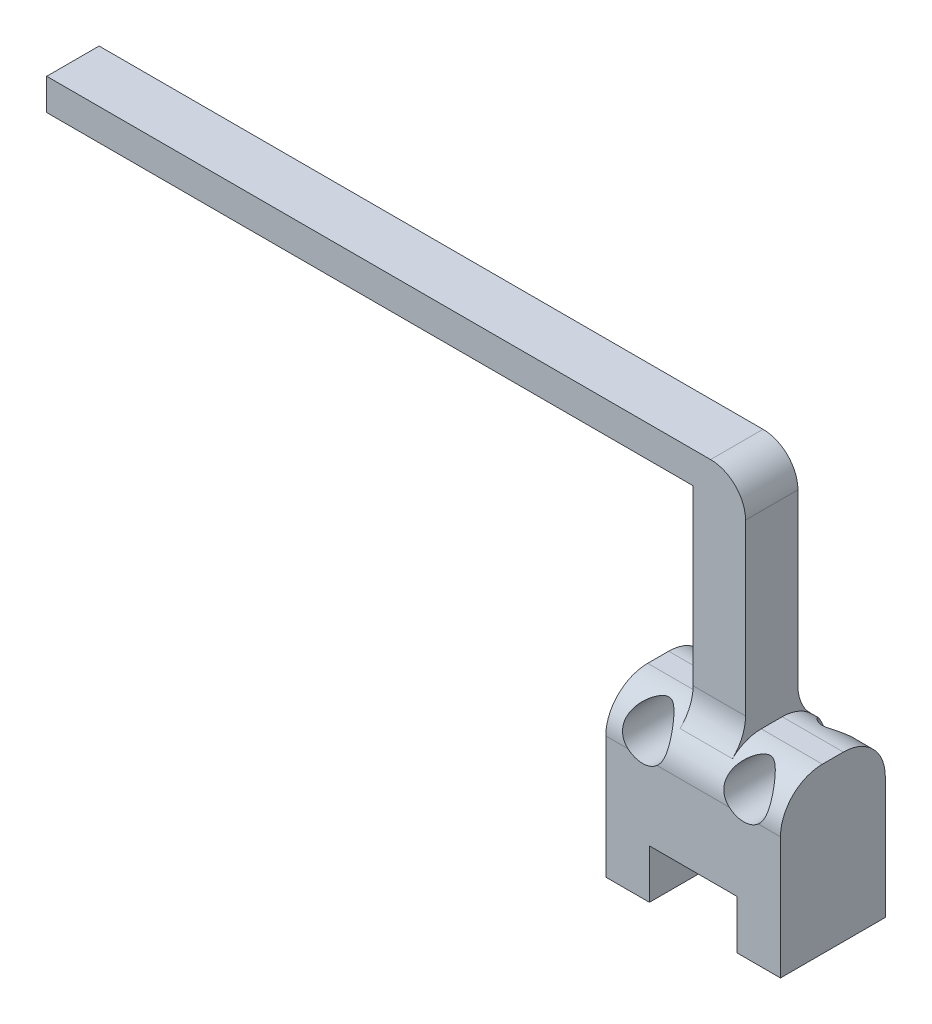
SolidWorks part; units mm, degrees
ref_plane "Front Plane" through (0, 0, 0) normal (0, 0, 1) x (1, 0, 0)
ref_plane "Top Plane" through (0, 0, 0) normal (0, 1, 0) x (1, 0, 0)
ref_plane "Right Plane" through (0, 0, 0) normal (1, 0, 0) x (0, 0, -1)
sketch "Sketch1" plane through (0, 0, 0) normal (0, 0, 1) x (1, 0, 0)
  line L19 (51.6669, -45.781) -> (59.1669, -45.781)
  line L20 (51.6669, -45.781) -> (41.6669, -45.781) construction
  line L21 (40.4169, -62.281) -> (52.9169, -62.281)
  line L22 (40.4169, -62.281) -> (40.4169, -69.281)
  line L24 (52.9169, -62.281) -> (52.9169, -69.281)
  line L25 (59.1669, -69.281) -> (34.1669, -69.281)
  line L28 (34.1669, -45.781) -> (41.6669, -45.781)
  line L32 (41.6669, -45.781) -> (51.6669, -45.781)
  line L33 (34.1669, -45.781) -> (34.1669, -69.281)
  line L34 (59.1669, -45.781) -> (59.1669, -69.281)
  line L35 (59.1669, -49.381) -> (34.1669, -49.381) construction
  line L36 (46.6669, -49.381) -> (46.6669, -45.781) construction
  circle A0 centre (53.9169, -49.381) radius 3.175
  circle A1 centre (39.4169, -49.381) radius 3.175
  point P0 (0, 0)
  point P9 (50, -65.781)
  point P11 (40.4169, -65.781)
  point P12 (46.6669, -47.581)
  dimension "D7" = 6.35
  dimension "D3" = 12.5
  dimension "D4" = 3.6
  dimension "D8" = 7.5
  dimension "D9" = 7.5
  dimension "D10" = 23.5
  dimension "D11" = 7
  dimension "D12" = 6.25
  dimension "D13" = 14.5
  dimension "D14" = 7.25
extrude "pusher base" add sketch "Sketch1" along normal blind 15 contours L32 L28 L19 A1 A0 L21 L24 L22 region at (46.6669, -57.06, 0)
sketch "Sketch3" plane through (0, -62.281, 0) normal (0, -1, 0) x (1, 0, 0)
  line L0 (46.6669, 15) -> (46.6669, 0) construction
  line L1 (40.4169, 15) -> (52.9169, 15) construction
  line L2 (40.4169, 0) -> (52.9169, 0) construction
  circle A0 centre (46.6669, 7.5) radius 1.95
  point P10 (46.6669, 7.5)
  dimension "D1" = 3.9
extrude "screw hole" cut sketch "Sketch3" against normal blind 7.5
ref_plane "Plane1" through (0, 0, 7.5) normal (0, 0, 1) x (1, 0, 0)
sketch "Sketch6" plane through (0, 0, 7.5) normal (0, 0, 1) x (1, 0, 0)
  line L0 (40.4169, -62.281) -> (52.9169, -62.281) construction
  line L5 (34.1669, -45.781) -> (59.1669, -45.781) construction
  line L6 (42.9169, -23.781) -> (50.4169, -23.781)
  line L11 (42.9169, -23.781) -> (42.9169, -45.781)
  line L12 (42.9169, -45.781) -> (50.4169, -45.781)
  line L13 (50.4169, -23.781) -> (50.4169, -45.781)
  line L14 (46.6669, -62.281) -> (46.6669, -29.281) construction
  line L15 (50.4169, -23.781) -> (42.9169, -23.781)
  line L16 (50.4169, -23.781) -> (50.4169, -13.781)
  line L17 (50.4169, -13.781) -> (42.9169, -13.781)
  line L18 (42.9169, -23.781) -> (42.9169, -13.781)
  point P2 (46.6669, -23.781)
  point P8 (46.6669, -45.781)
  dimension "D1" = 7.5
  dimension "D3" = 7.5
  dimension "D4" = 10
  dimension "D5" = 38.5
extrude "pusher head" add sketch "Sketch6" along normal mid plane 7.5 contours L18 L15 L6 L16 L17 | L13 L6 L12 | L11 L12 L6 region at (46.6669, -18.781, 7.5) region at (46.6669, -34.781, 7.5)
fillet "Fillet1" radius 6 2 edges at (46.6669, -45.781, 0) (46.6669, -45.781, 15)
fillet "Fillet5" radius 6 1 edges at (46.6669, -46.2189, 11.25)
fillet "Fillet6" radius 6 1 edges at (46.6669, -46.2189, 3.75)
sketch "Sketch8" plane through (0, 0, 3.75) normal (0, 0, -1) x (-1, 0, 0)
  line L1 (-42.9169, -13.781) -> (49.5831, -13.781)
  line L2 (-42.9169, -13.781) -> (-42.9169, -18.281)
  line L3 (-42.9169, -18.281) -> (49.5831, -18.281)
  line L4 (49.5831, -13.781) -> (49.5831, -18.281)
  dimension "D1" = 92.5
  dimension "D2" = 4.5
extrude "Boss-Extrude1" add sketch "Sketch8" against normal blind 7.5
fillet "Fillet7" radius 5 1 edges at (50.4169, -13.781, 7.5)
equation "\"PusherHeight\"=2"
equation "\"PusherWidth\"=11"
equation "\"PusherLongWidth\"=5"
equation "\"RodDiameter\"=0.5"
equation "\"HookLength\"=2.01152"
equation "\"HookHeight\"=0.999652"
equation "\"HookInnerLength\"=2"
equation "\"RodHeightDistance\"=0.4276"
equation "\"RodWidthDistance\"=0.75"
equation "\"PusherDepth\"=2"
equation "\"BuckleShaftDiameter\"=0.383646"
equation "\"BeltBuckleDistance\"=1.5"
equation "\"DowelDiameter\"=0.635"
equation "\"D7@Sketch1\"=\"DowelDiameter\""
equation "\"RodSeperationDistance\"=3.98"
equation "\"BuckleNutDiameter\"=0.39"
equation "\"D1@Sketch3\"=\"BuckleNutDiameter\""
equation "\"belt hole width\"=1.4"
equation "\"pusher height\"=3.5175"
equation "\"pusher slot width\"=0.75"
equation "\"D1@Sketch6\"=\"pusher slot width\""
equation "\"pushing bar width\"=1"
equation "\"D4@Sketch6\"=\"pushing bar width\""
equation "\"doweltotop\"=0.36"
equation "\"D4@Sketch1\"=\"doweltotop\""
equation "\"dowel separation\"=1.45"
equation "\"D13@Sketch1\"=\"dowel separation\""
